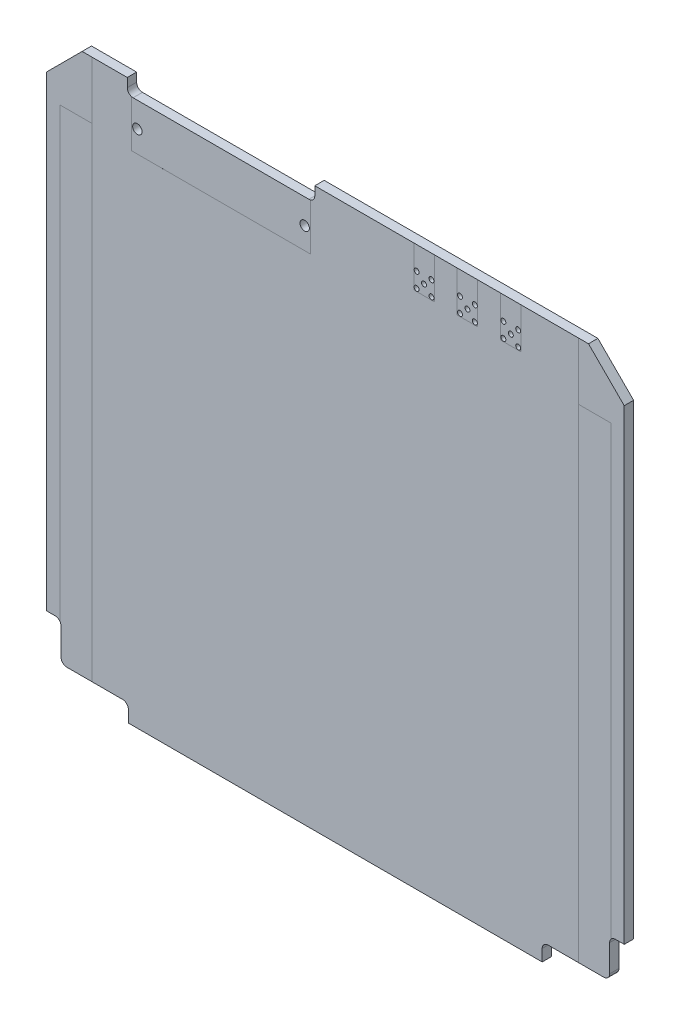
SolidWorks part; units mm, degrees
material "FR4_stuffedProtoboard"
ref_plane "Front Plane" through (0, 0, 0) normal (0, 0, 1) x (1, 0, 0)
ref_plane "Top Plane" through (0, 0, 0) normal (0, 1, 0) x (1, 0, 0)
ref_plane "Right Plane" through (0, 0, 0) normal (1, 0, 0) x (0, 0, -1)
ref_plane "Plane4" through (0, 0, -0.0125) normal (0, 0, -1) x (-1, 0, 0)
sketch "Sketch1" plane through (0, 0, -0.0125) normal (0, 0, -1) x (-1, 0, 0)
  line L0 (35.3, -50) -> (35.3, -48)
  line L1 (36.3, -47) -> (45.8, -47)
  line L2 (46.8, -46) -> (46.8, -41.4)
  line L3 (47.8, -40.4) -> (49.3, -40.4)
  line L4 (49.3, -40.4) -> (49.3, 39.2)
  line L5 (49.3, 39.2) -> (43.2, 45.3)
  line L6 (43.2, 45.3) -> (35.5, 45.3)
  line L7 (35.5, 45.3) -> (35.5, 43.8)
  line L8 (34.5, 42.8) -> (4.5, 42.8)
  line L9 (3.5, 43.8) -> (3.5, 45.3)
  line L10 (3.5, 45.3) -> (-43.2, 45.3)
  line L11 (-43.2, 45.3) -> (-49.3, 39.2)
  line L12 (-49.3, 39.2) -> (-49.3, -40.4)
  line L13 (-49.3, -40.4) -> (-47.8, -40.4)
  line L14 (-46.8, -41.4) -> (-46.8, -46)
  line L15 (-45.8, -47) -> (-36.3, -47)
  line L16 (-35.3, -48) -> (-35.3, -50)
  line L17 (-35.3, -50) -> (35.3, -50)
  line L18 (0, -50) -> (0, 45.3) construction
  line L19 (19.5, 42.8) -> (19.5, 25.5258) construction
  line L20 (-13.87, 41.37) -> (-16.41, 38.83) construction
  line L21 (-21.27, 41.37) -> (-23.81, 38.83) construction
  line L22 (-28.67, 41.37) -> (-31.21, 38.83) construction
  arc A0 (35.3, -48) -> (36.3, -47) centre (36.3, -48) cw
  arc A1 (45.8, -47) -> (46.8, -46) centre (45.8, -46) ccw
  arc A2 (46.8, -41.4) -> (47.8, -40.4) centre (47.8, -41.4) cw
  arc A3 (35.5, 43.8) -> (34.5, 42.8) centre (34.5, 43.8) cw
  arc A4 (4.5, 42.8) -> (3.5, 43.8) centre (4.5, 43.8) cw
  arc A5 (-47.8, -40.4) -> (-46.8, -41.4) centre (-47.8, -41.4) cw
  arc A6 (-46.8, -46) -> (-45.8, -47) centre (-45.8, -46) ccw
  arc A7 (-36.3, -47) -> (-35.3, -48) centre (-36.3, -48) cw
  circle A8 centre (-21.27, 41.37) radius 0.425
  circle A9 centre (-23.81, 41.37) radius 0.425
  circle A10 centre (-22.54, 40.1) radius 0.425
  circle A11 centre (-13.87, 41.37) radius 0.425
  circle A12 centre (-23.81, 38.83) radius 0.425
  circle A13 centre (-16.41, 41.37) radius 0.425
  circle A14 centre (-15.14, 40.1) radius 0.425
  circle A15 centre (-21.27, 38.83) radius 0.425
  circle A16 centre (-28.67, 41.37) radius 0.425
  circle A17 centre (-31.21, 41.37) radius 0.425
  circle A18 centre (-16.41, 38.83) radius 0.425
  circle A19 centre (-29.94, 40.1) radius 0.425
  circle A20 centre (-31.21, 38.83) radius 0.425
  circle A21 centre (-28.67, 38.83) radius 0.425
  circle A22 centre (33.775, 38.54) radius 0.8
  circle A23 centre (5.225, 38.54) radius 0.8
  circle A24 centre (-13.87, 38.83) radius 0.425
  point P35 (-15.14, 40.1)
  dimension "D7" = 2.5
  dimension "D8" = 1.6
  dimension "D9" = 14.275
  dimension "D10" = 4.26
  dimension "D11" = 1
  dimension "D12" = 1
  dimension "D13" = 1
  dimension "D14" = 1
  dimension "D15" = 1
  dimension "D16" = 1
  dimension "D17" = 1
  dimension "D18" = 1
  dimension "D26" = 0.85
  dimension "D1" = 98.6
  dimension "D2" = 95.3
  dimension "D3" = 14
  dimension "D4" = 9.6
  dimension "D5" = 2.5
  dimension "D6" = 3
  dimension "D19" = 14
  dimension "D20" = 2.5
  dimension "D21" = 6.1
  dimension "D22" = 6.1
  dimension "D23" = 32
  dimension "D24" = 2.54
  dimension "D25" = 2.54
  dimension "D28" = 7.4
  dimension "D29" = 3.93
  dimension "D30" = 35.43
  dimension "D31" = 45
  dimension "D32" = 45
  dimension "D33" = 29.8
  dimension "D34" = 50
  dimension "D27" = 3
extrude "Boss-Extrude1" add sketch "Sketch1" against normal blind 1.6
sketch "thermalContacts_lower" plane through (0, 0, -0.0125) normal (0, 0, -1) x (-1, 0, 0)
  line L3 (47, 35.5) -> (47, -41.5)
  line L4 (41.5, 35.5) -> (41.5, 41.5)
  line L5 (41.5, 35.5) -> (47, 35.5)
  line L9 (-47, 35.5) -> (-47, -41.1726)
  line L10 (-41.5, 35.5) -> (-47, 35.5)
  line L11 (-41.5, 35.5) -> (-41.5, 42.5522)
  line L14 (-41.5, 42.5522) -> (-41.5, 47.8583)
  line L18 (41.5, 41.5) -> (41.5, 47)
  line L20 (47, -41.5) -> (59.8273, -41.5)
  line L21 (59.8273, -41.5) -> (59.8273, 47)
  line L22 (-54.1782, 47.8583) -> (-41.5, 47.8583)
  line L23 (41.5, 47) -> (59.8273, 47)
  line L24 (-54.1782, 47.8583) -> (-54.1782, -41.1726)
  line L25 (-47, -41.1726) -> (-54.1782, -41.1726)
  line L26 (43.2, 45.3) -> (35.5, 45.3) construction
  line L27 (49.3, -40.4) -> (49.3, 39.2) construction
  line L28 (3.5, 45.3) -> (-43.2, 45.3) construction
  line L29 (-49.3, 39.2) -> (-49.3, -40.4) construction
  dimension "D1" = 9.8
  dimension "D2" = 7.8
  dimension "D3" = 2.3
  dimension "D4" = 9.8
  dimension "D5" = 7.8
  dimension "D6" = 2.3
sketch "thermalContacts_upper" plane through (0, 0, 1.5875) normal (0, 0, 1) x (1, 0, 0)
  line L3 (-47, 35.5) -> (-47, -41.5)
  line L4 (-41.5, 35.5) -> (-41.5, 41.5)
  line L5 (-41.5, 35.5) -> (-47, 35.5)
  line L9 (47, 35.5) -> (47, -41.5)
  line L10 (41.5, 35.5) -> (47, 35.5)
  line L11 (41.5, 35.5) -> (41.5, 41.5)
  line L14 (41.5, 41.5) -> (41.5, 47)
  line L15 (41.5, 41.5) -> (49.5, 41.5) construction
  line L18 (-41.5, 41.5) -> (-41.5, 47)
  line L19 (-41.5, 41.5) -> (-49.5, 41.5) construction
  line L20 (47, -41.5) -> (59.8273, -41.5)
  line L21 (59.8273, -41.5) -> (59.8273, 47)
  line L22 (59.8273, 47) -> (41.5, 47)
  line L23 (-41.5, 47) -> (-56.1922, 47)
  line L24 (-56.1922, 47) -> (-56.1922, -41.5)
  line L25 (-56.1922, -41.5) -> (-47, -41.5)
extrude "keepOut_top" cut sketch "thermalContacts_lower" against normal blind 0.0001
extrude "keepOut_bottom" cut sketch "thermalContacts_upper" against normal blind 0.0001
sketch "partFootprints" plane through (0, 0, 1.5875) normal (0, 0, 1) x (1, 0, 0)
  line L0 (-34.74, 34.84) -> (-34.74, 42.8292)
  line L1 (-4.26, 34.84) -> (-34.74, 34.84)
  line L2 (-41.5, 45.3) -> (-35.5, 45.3) construction
  line L3 (-36.1132, 45.3) -> (-39.5054, 45.3) construction
  line L4 (-4.26, 34.84) -> (-4.26, 42.8292)
  line L5 (-49.3, -40.4) -> (-49.3, 39.2) construction
  line L6 (13.39, 45.3) -> (13.39, 38.35)
  line L7 (13.39, 38.35) -> (16.89, 38.35)
  line L8 (16.89, 38.35) -> (16.89, 45.3)
  line L9 (16.89, 45.3) -> (13.39, 45.3)
  line L10 (20.79, 45.3) -> (20.79, 38.35)
  line L11 (20.79, 38.35) -> (24.29, 38.35)
  line L12 (24.29, 38.35) -> (24.29, 45.3)
  line L13 (24.29, 45.3) -> (20.79, 45.3)
  line L14 (28.19, 45.3) -> (28.19, 38.35)
  line L15 (28.19, 38.35) -> (31.69, 38.35)
  line L16 (31.69, 38.35) -> (31.69, 45.3)
  line L17 (31.69, 45.3) -> (28.19, 45.3)
  line L18 (49.3, -40.4) -> (49.3, 39.2) construction
  line L20 (-34.74, 42.8292) -> (-4.26, 42.8292)
  line L21 (-3.5, 45.3) -> (41.5, 45.3) construction
  line L22 (14.12, 38.35) -> (15.8235, 38.35) construction
  line L25 (13.39, 42.2411) -> (13.39, 38.35) construction
  line L26 (16.89, 41.85) -> (16.89, 38.35) construction
  arc A0 (-35.5, 43.8) -> (-34.5, 42.8) centre (-34.5, 43.8) ccw construction
  arc A1 (-4.5, 42.8) -> (-3.5, 43.8) centre (-4.5, 43.8) ccw construction
  dimension "D1" = 10.46
  dimension "D2" = 14.56
  dimension "D3" = 30.48
  dimension "D4" = 6.95
  dimension "D5" = 17.61
  dimension "D7" = 7.4
  dimension "D8" = 3.5
  dimension "D6" = 3
extrude "footPrints" cut sketch "partFootprints" against normal blind 0.0001
sketch "Sketch3" plane through (0, 0, 1.5875) normal (0, 0, 1) x (1, 0, 0)
  line L1 (41.5, -47) -> (41.5, 35.5)
  line L2 (47, 35.5) -> (47, -40.8) construction
  line L3 (46.8, -41.4) -> (46.8, -46) construction
  line L4 (45.8, -47) -> (36.3, -47) construction
  line L5 (47, 35.5) -> (47, -40.8)
  line L6 (46.8, -41.4) -> (46.8, -46)
  line L7 (45.8, -47) -> (41.5, -47)
  line L8 (41.5, 35.5) -> (47, 35.5) construction
  line L9 (41.5, 35.5) -> (47, 35.5)
  line L10 (0, -50) -> (0, 45.3) construction
  line L11 (35.3, -50) -> (-35.3, -50) construction
  line L12 (-3.5, 45.3) -> (13.39, 45.3) construction
  line L13 (-41.5, 35.5) -> (-47, 35.5)
  line L14 (-45.8, -47) -> (-41.5, -47)
  line L15 (-46.8, -41.4) -> (-46.8, -46)
  line L16 (-47, 35.5) -> (-47, -40.8)
  line L17 (-41.5, -47) -> (-41.5, 35.5)
  line L18 (41.5, 45.3) -> (41.5, 35.5) construction
  arc A0 (47, -40.8) -> (46.8, -41.4) centre (47.8, -41.4) ccw construction
  arc A1 (45.8, -47) -> (46.8, -46) centre (45.8, -46) ccw construction
  arc A2 (47, -40.8) -> (46.8, -41.4) centre (47.8, -41.4) ccw
  arc A3 (45.8, -47) -> (46.8, -46) centre (45.8, -46) ccw
  arc A4 (-45.8, -47) -> (-46.8, -46) centre (-45.8, -46) cw
  arc A5 (-47, -40.8) -> (-46.8, -41.4) centre (-47.8, -41.4) cw
extrude "caution_top" cut sketch "Sketch3" against normal blind 0.0001
ref_plane "midplane_Z" through (0, 0, 0.7875) normal (0, 0, 1) x (1, 0, 0)
mirror "caution_bottom" about plane through (0, 0, 0.7875) normal (0, 0, 1) of "caution_top"
ref_point "rail midpoint"
